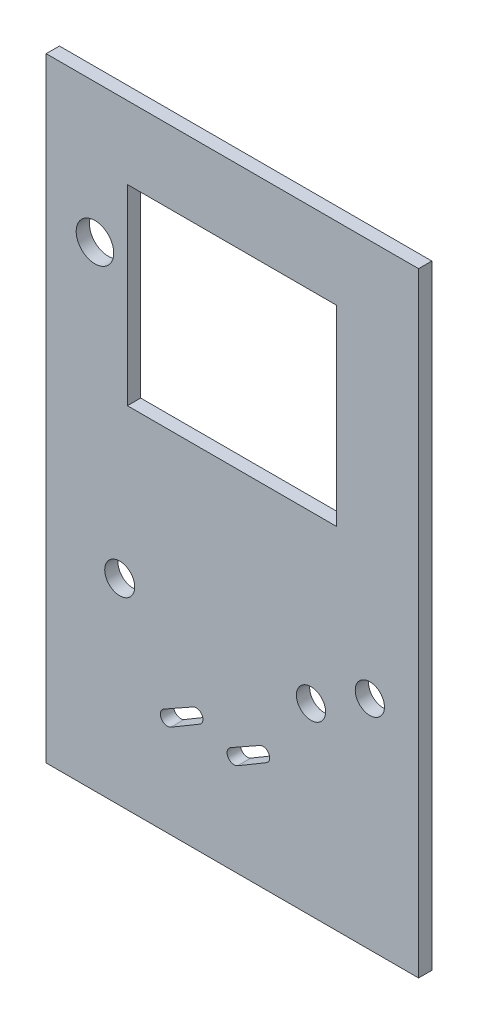
SolidWorks part; units mm, degrees
ref_plane "Front Plane" through (0, 0, 0) normal (0, 0, 1) x (1, 0, 0)
ref_plane "Top Plane" through (0, 0, 0) normal (0, 1, 0) x (1, 0, 0)
ref_plane "Right Plane" through (0, 0, 0) normal (1, 0, 0) x (0, 0, -1)
sketch "Sketch1" plane through (0, 0, 0) normal (0, 0, 1) x (1, 0, 0)
  line L0 (0.1058, 73.6301) -> (-0.0148, 62.4901) construction
  line L1 (-0.0148, 62.4901) -> (-0.0148, 56.2001) construction
  line L2 (-0.0148, 56.2001) -> (-0.0148, 10.268) construction
  line L3 (-15.4692, -49.8142) -> (-8.5409, -45.8142) construction
  line L4 (-15.4692, -49.8142) -> (0.5308, -49.8142) construction
  line L5 (0.5308, -49.8142) -> (7.4591, -45.8142) construction
  line L6 (-0.0148, 10.268) -> (0.1058, -73.6642) construction
  line L15 (-16.3293, -29.1587) -> (-16.3293, -23.8757)
  line L20 (-0.2968, -48.3429) -> (6.6759, -44.4208)
  line L21 (8.2583, -47.1985) -> (1.3584, -51.2855)
  line L22 (-44.5392, 73.6301) -> (44.7508, 73.6301)
  line L23 (44.7508, 73.6301) -> (44.7508, -73.6642)
  line L24 (44.7508, -73.6642) -> (-44.5392, -73.6642)
  line L25 (-44.5392, -73.6642) -> (-44.5392, 73.6301)
  line L26 (-25.0598, 56.2001) -> (-25.0598, 10.268)
  line L27 (-25.0598, 10.268) -> (25.0303, 10.268)
  line L28 (25.0303, 10.268) -> (25.0303, 56.2001)
  line L29 (25.0303, 56.2001) -> (-25.0598, 56.2001)
  line L34 (35.8896, 62.4901) -> (-35.9192, 62.4901)
  line L35 (-38.4192, 59.9901) -> (-38.4192, 6.918)
  line L36 (-35.9192, 4.418) -> (29.9974, 4.418)
  line L37 (38.3896, 13.668) -> (38.3896, 59.9901)
  line L38 (-16.2968, -48.3429) -> (-9.3241, -44.4208)
  line L39 (-7.7417, -47.1985) -> (-14.6416, -51.2855)
  line L150 (42.2525, -55.0539) -> (42.2511, -54.9499)
  circle A2 centre (-26.9008, -26.5172) radius 3.6
  arc A3 (8.2583, -47.1985) -> (6.6759, -44.4208) centre (7.4591, -45.8142) ccw
  arc A6 (-16.2968, -48.3429) -> (-14.6416, -51.2855) centre (-15.4692, -49.8142) ccw
  arc A7 (-7.7417, -47.1985) -> (-9.3241, -44.4208) centre (-8.5409, -45.8142) ccw
  circle A15 centre (18.9576, -29.5613) radius 3.5
  circle A16 centre (33.0683, -21.4917) radius 3.5
  arc A17 (-0.2968, -48.3429) -> (1.3584, -51.2855) centre (0.5308, -49.8142) ccw
  circle A19 centre (-32.8459, 40.326) radius 4.5
  arc A24 (38.3896, 59.9901) -> (35.8896, 62.4901) centre (35.8896, 59.9901) ccw
  arc A25 (-35.9192, 62.4901) -> (-38.4192, 59.9901) centre (-35.9192, 59.9901) ccw
  arc A26 (-38.4192, 6.918) -> (-35.9192, 4.418) centre (-35.9192, 6.918) ccw
  arc A27 (29.9974, 4.418) -> (38.3896, 13.668) centre (29.1397, 13.6282) ccw
  dimension "D4" = 11.14
  dimension "D8" = 7
  dimension "D11" = 9
  dimension "D12" = 7.2
  dimension "D14" = 9.25
  dimension "D15" = 2.5
  dimension "D2" = 89.29
  dimension "D3" = 147.2943
  dimension "D5" = 25.9097
  dimension "D6" = 8.0696
  dimension "D7" = 14.1107
  dimension "D9" = 7.7861
  dimension "D10" = 22.1641
  dimension "D13" = 10.5715
  dimension "D16" = 6.29
  dimension "D17" = 6.12
  dimension "D18" = 5.85
  dimension "D19" = 16
  dimension "D20" = 8
  dimension "D21" = 29.07
  dimension "D22" = 23.85
  dimension "D23" = 30
extrude "Bezel" add sketch "Sketch1<6>" along normal blind 3.18 contours L36 A27 L37 A24 L34 A25 L35 A26 L29 L28 L27 L26 A19 region at (36.9765, 61.077, 0)
sketch "Sketch1<6>" plane through (0, 0, 0) normal (0, 0, 1) x (1, 0, 0) same geometry as "Sketch1"
extrude "Body" add sketch "Sketch1" along normal blind 3.18 contours L25 L24 L23 L22 A27 L36 A26 L35 A25 L34 A24 L37 A17 L20 A3 L21 A16 A15 A7 L39 A6 L38 A2 region at (0.1688, -16.746, 0)
